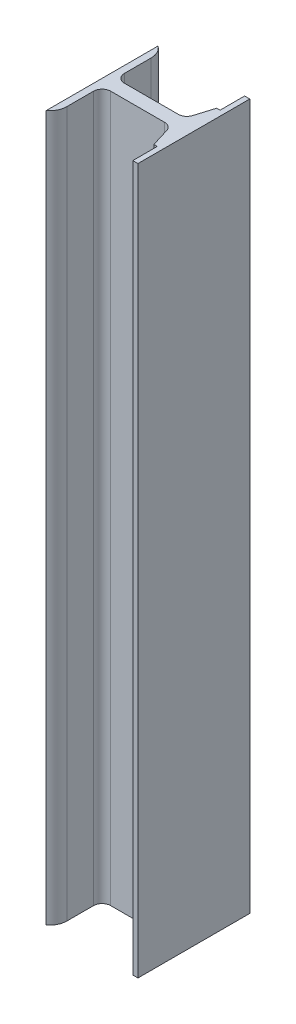
SolidWorks part; units mm, degrees
ref_plane "Front Plane" through (0, 0, 0) normal (0, 0, 1) x (1, 0, 0)
ref_plane "Top Plane" through (0, 0, 0) normal (0, 1, 0) x (1, 0, 0)
ref_plane "Right Plane" through (0, 0, 0) normal (1, 0, 0) x (0, 0, -1)
sketch "Sketch1" plane through (0, 0, 0) normal (0, 1, 0) x (1, 0, 0)
  line L16 (-113.9237, 64.9118) -> (-73.9237, 64.9118)
  line L18 (-73.9237, 56.9118) -> (-113.9237, 56.9118)
  line L21 (-113.9237, 93.4118) -> (-113.9237, 64.9118)
  line L22 (-67.5927, 93.4118) -> (-64.5927, 93.4118)
  line L23 (-64.5927, 93.4118) -> (-64.5927, 28.4118)
  line L24 (-64.5927, 28.4118) -> (-67.5927, 28.4118)
  line L25 (-67.5927, 28.4118) -> (-67.5927, 42.6618)
  line L26 (-67.5927, 42.6618) -> (-69.5927, 42.6618)
  line L27 (-67.5927, 93.4118) -> (-67.5927, 79.1618)
  line L28 (-67.5927, 79.1618) -> (-69.5927, 79.1618)
  line L29 (-69.5927, 79.1618) -> (-73.9237, 64.9118)
  line L30 (-69.5927, 42.6618) -> (-73.9237, 56.9118)
  line L31 (-113.9237, 93.4118) -> (-117.9237, 93.4118)
  line L32 (-117.9237, 93.4118) -> (-117.9237, 28.4118)
  line L33 (-117.9237, 28.4118) -> (-113.9237, 28.4118)
  line L34 (-113.9237, 28.4118) -> (-113.9237, 56.9118)
extrude "Boss-Extrude2" add sketch "Sketch1" along normal blind 410
fillet "Fillet1" radius 10 2 edges at (-113.9237, 205, -93.4118) (-113.9237, 205, -28.4118)
fillet "Fillet2" radius 5 4 edges at (-73.9237, 205, -64.9118) (-73.9237, 205, -56.9118) (-113.9237, 205, -64.9118) (-113.9237, 205, -56.9118)
sketch "Sketch2" plane through (0, 410, 0) normal (0, 1, 0) x (1, 0, 0)
